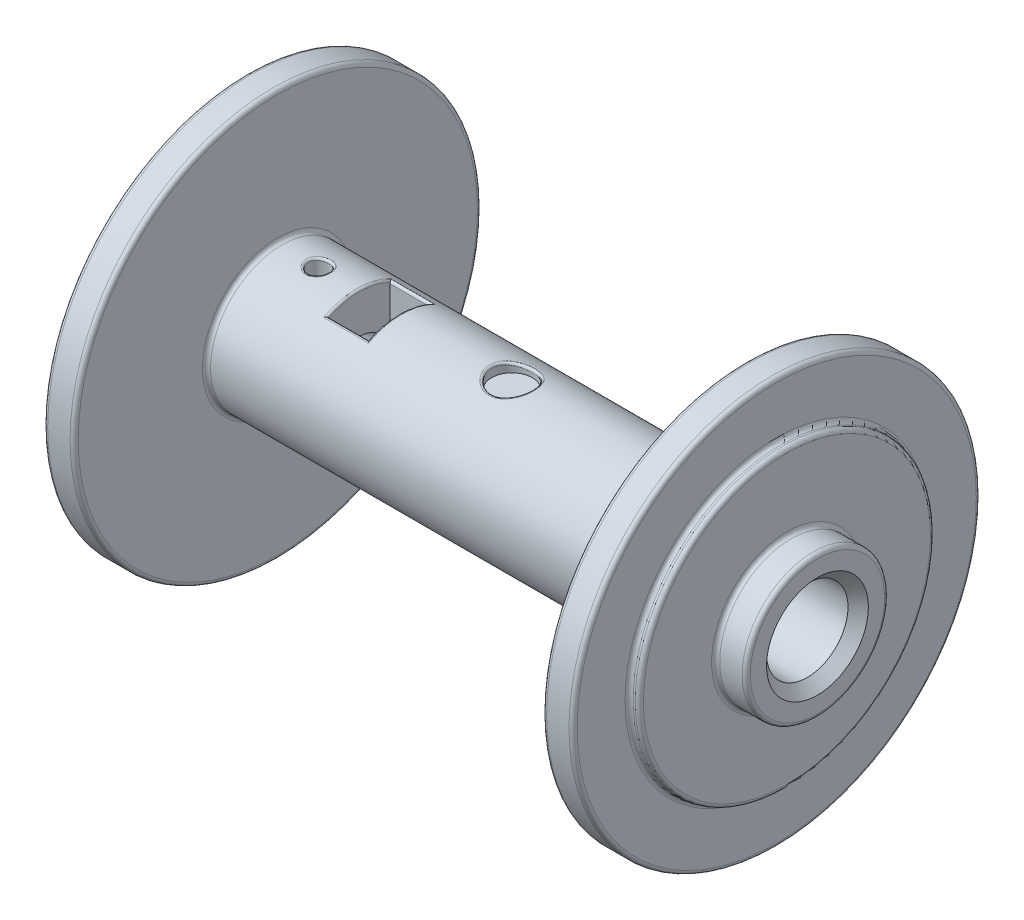
SolidWorks part; units mm, degrees
ref_plane "前视基准面" through (0, 0, 0) normal (0, 0, 1) x (1, 0, 0)
ref_plane "上视基准面" through (0, 0, 0) normal (0, 1, 0) x (1, 0, 0)
ref_plane "右视基准面" through (0, 0, 0) normal (1, 0, 0) x (0, 0, -1)
sketch "草图1" plane through (0, 0, 0) normal (1, 0, 0) x (0, 0, -1)
  circle A0 centre (0, 0) radius 10
  dimension "D1" = 20
extrude "凸台-拉伸1" add sketch "草图1" along normal blind 1.5
sketch "草图2" plane through (0, 0, 0) normal (-1, 0, 0) x (0, 0, 1)
  circle A0 centre (0, 0) radius 7.25
  dimension "D1" = 14.5
extrude "凸台-拉伸2" add sketch "草图2" along normal blind 0.5
sketch "草图3" plane through (-0.5, 0, 0) normal (-1, 0, 0) x (0, 0, 1)
  circle A0 centre (0, 0) radius 3.5
  dimension "D1" = 7
extrude "凸台-拉伸3" add sketch "草图3" along normal blind 1.5
sketch "草图4" plane through (1.5, 0, 0) normal (1, 0, 0) x (0, 0, -1)
  circle A0 centre (0, 0) radius 3.5
  dimension "D1" = 7
extrude "凸台-拉伸4" add sketch "草图4" along normal blind 23
sketch "草图5" plane through (24.5, 0, 0) normal (1, 0, 0) x (0, 0, -1)
  circle A0 centre (0, 0) radius 10
  dimension "D1" = 20
extrude "凸台-拉伸5" add sketch "草图5" along normal blind 1.5
sketch "草图6" plane through (26, 0, 0) normal (1, 0, 0) x (0, 0, -1)
  circle A0 centre (0, 0) radius 7.25
  dimension "D1" = 14.5
extrude "凸台-拉伸6" add sketch "草图6" along normal blind 0.5
sketch "草图7" plane through (26.5, 0, 0) normal (1, 0, 0) x (0, 0, -1)
  circle A0 centre (0, 0) radius 3.5
  dimension "D1" = 7
extrude "凸台-拉伸7" add sketch "草图7" along normal blind 1.5
sketch "草图8" plane through (-2, 0, 0) normal (-1, 0, 0) x (0, 0, 1)
  circle A0 centre (0, 0) radius 1.5
  dimension "D1" = 3
extrude "切除-拉伸1" cut sketch "草图8" against normal blind 7.5
sketch "草图9" plane through (28, 0, 0) normal (1, 0, 0) x (0, 0, -1)
  circle A0 centre (0, 0) radius 2
  dimension "D1" = 4
extrude "切除-拉伸2" cut sketch "草图9" against normal blind 22
sketch "草图10" plane through (0, 0, 0) normal (0, 1, 0) x (1, 0, 0)
  line L0 (-2, 0) -> (3.5, 0) construction
  line L1 (-2, 3.5) -> (-2, -3.5) construction
  line L2 (3.5, 0) -> (5.5, 0) construction
  line L3 (5.5, 0) -> (7.5, 0) construction
  line L5 (5.5, -1.5) -> (7.5, -1.5)
  line L6 (5.5, 1.5) -> (7.5, 1.5)
  line L7 (7.5, 1.5) -> (7.5, -1.5)
  line L8 (5.5, 1.5) -> (5.5, -1.5)
  circle A0 centre (3.5, 0) radius 0.5
  dimension "D4" = 1
  dimension "D1" = 5.5
  dimension "D2" = 2
  dimension "D3" = 2
  dimension "D5" = 1.5
  dimension "D6" = 1.5
extrude "切除-拉伸3" cut sketch "草图10" against normal up to next and the other way up to next
sketch "草图11" plane through (6, 0, 0) normal (1, 0, 0) x (0, 0, -1)
  line L0 (0, 2) -> (0, -2) construction
  line L1 (-1.5, 1.3229) -> (-1.5, -1.3229)
  line L2 (1.5, 1.3229) -> (1.5, -1.3229)
  line L4 (-1.5, 2) -> (-1.5, -2) construction
  line L5 (1.5, 2) -> (1.5, -2) construction
  arc A0 (-1.5, 1.3229) -> (-1.5, -1.3229) centre (0, 0) ccw
  arc A1 (1.5, -1.3229) -> (1.5, 1.3229) centre (0, 0) ccw
  dimension "D1" = 4
  dimension "D2" = 1.5
  dimension "D3" = 1.5
extrude "凸台-拉伸8" add sketch "草图11" along normal blind 7.5
sketch "草图12" plane through (0, 0, 0) normal (0, 1, 0) x (1, 0, 0)
  line L0 (-2, 0) -> (13, 0) construction
  line L1 (-2, 3.5) -> (-2, -3.5) construction
  circle A0 centre (13, 0) radius 1
  dimension "D2" = 2
  dimension "D1" = 15
extrude "切除-拉伸4" cut sketch "草图12" against normal up to next from offset 3 offset against normal yes
mirror "镜向1" about plane through (0, 0, 0) normal (0, 1, 0) of "切除-拉伸4"
chamfer "倒角1" distance 0.5 angle 45 1 edges at (28, 0, -2)
fillet "圆角1" radius 0.2 14 edges at (26.5, 0, -3.5) (26.5, 0, -7.25) (26, 0, -7.25) (26, 0, -10) (24.5, 0, -3.5) (24.5, 0, -10) (1.5, 0, -3.5) (1.5, 0, -10) (0, 0, -7.25) (0, 0, -10) (-0.5, 0, 3.5) (-0.5, 0, 7.25) (28, 0, -3.5) (-2, 0, 3.5)
fillet "圆角2" radius 0.1 12 edges at (3.3907, 3.4658, 0.4879) (3.6093, -3.4658, -0.4879) (5.5, 3.5, 0) (6.5, 3.1623, -1.5) (6.5, 3.1623, 1.5) (7.5, 3.5, 0) (12.8141, 3.3592, 0.9826) (13.1859, -3.3592, -0.9826) (6.5, -3.1623, -1.5) (7.5, -3.5, 0) (6.5, -3.1623, 1.5) (5.5, -3.5, 0)
